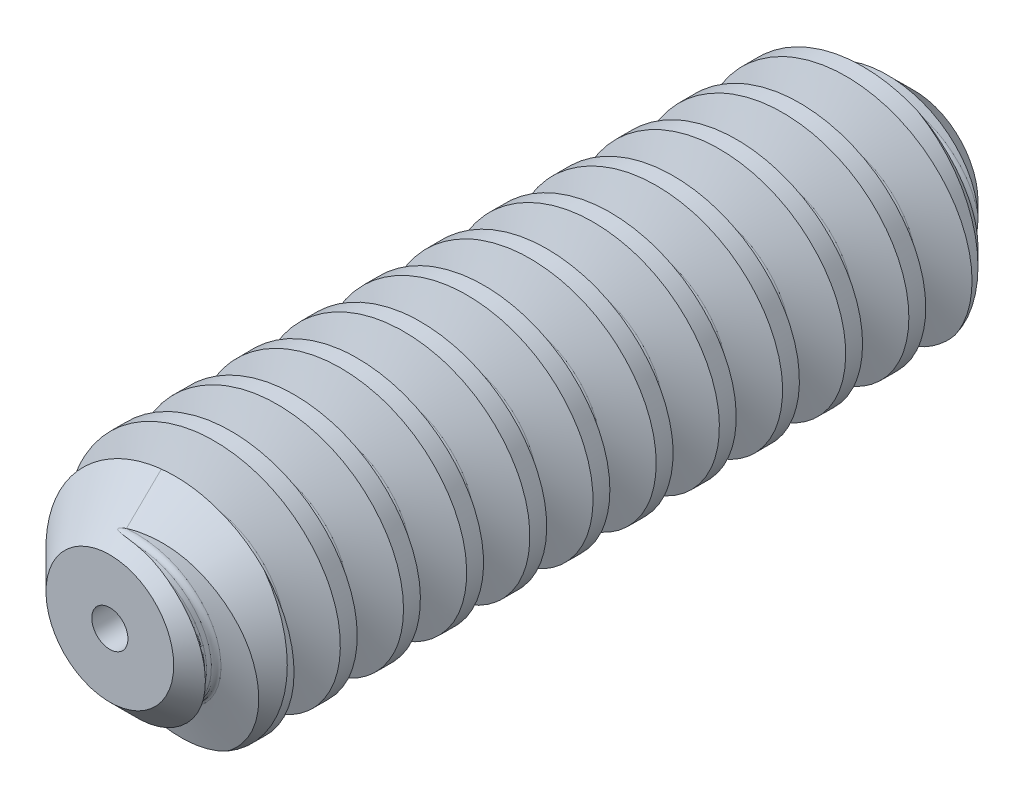
SolidWorks part; units mm, degrees
note: '?' marks a value the reader was unsure of.
ref_plane "Front Plane" through (0, 0, 0) normal (0, 0, 1) x (1, 0, 0)
ref_plane "Top Plane" through (0, 0, 0) normal (0, 1, 0) x (1, 0, 0)
ref_plane "Right Plane" through (0, 0, 0) normal (1, 0, 0) x (0, 0, -1)
ref_axis "Axis1" through (0, 0, 31.1561) along (0, 0, -1)?
sketch "SketchRevolveWorm01" plane through (0, 0, 0) normal (1, 0, 0) x (0, 0, -1)
  line L0 (0, 0) -> (1, 0) construction
  line L1 (10, 0) -> (10, 1.5878)
  line L2 (10, 1.5878) -> (8.5878, 3)
  line L3 (8.5878, 3) -> (-8.5878, 3)
  line L4 (-8.5878, 3) -> (-10, 1.5878)
  line L5 (-10, 1.5878) -> (-10, 0)
  line L6 (-10, 0) -> (10, 0)
  dimension "Side1" = 10
  dimension "ChamferX" = 1.4122
  dimension "ChamferY" = 1.4122
  dimension "OutsideDiameter" = 3
  dimension "WormLength" = 20
revolve "Worm01" add sketch "SketchRevolveWorm01" angle 360 about L0
ref_plane "HelixPlaneWorm01" through (0, 0, 10.9956) normal (0, 0, 1) x (1, 0, 0)
sketch "SketchHelixWorm01" plane through (0, 0, 10.9956) normal (0, 0, 1) x (1, 0, 0)
  circle A0 centre (0, 0) radius 2.5
  dimension "PitchDiameter" = 5
curve "GearHelixWorm01" pitch 1.5708 height 21.9911 turns 14
sketch "SketchToothWorm01" plane through (0, 0, 0) normal (0, 1, 0) x (1, 0, 0)
  line L0 (3.125, -10.3742) -> (1.9735, -10.7956)
  line L1 (1.875, -10.9364) -> (1.875, -11.0547)
  line L2 (1.9735, -11.1956) -> (3.125, -11.617)
  line L3 (3.125, -11.617) -> (3.125, -10.3742)
  arc A0 (1.9735, -10.7956) -> (1.875, -10.9364) centre (2.025, -10.9364) ccw
  arc A1 (1.875, -11.0547) -> (1.9735, -11.1956) centre (2.025, -11.0547) ccw
sweep "ToothCutWorm01" cut profiles "SketchToothWorm01" path "GearHelixWorm01"
sketch "BoreRevolveSketch" plane through (0, 0, 0) normal (1, 0, 0) x (0, 0, -1)
  line L0 (-10, 0) -> (10, 0)
  line L1 (10, 0) -> (10, 0.45)
  line L2 (10, 0.45) -> (-10, 0.45)
  line L3 (-10, 0.45) -> (-10, 0)
  dimension "BoreSide1" = 10
  dimension "TaperSide1" = 0.45
  dimension "BoreSide2" = 10
  dimension "TaperSide2" = 0.45
sketch "KeywaySketch" plane through (0, 0, 0) normal (0, 0, 1) x (1, 0, 0)
  line L0 (0, 0) -> (0.8988, 0) construction
sketch "AuxiliarySketchWorm01" plane through (0, 0, 0) normal (0, 0, 1) x (1, 0, 0)
  circle A0 centre (0, 0) radius 2.5 construction
  dimension "PitchDiameter" = 5
sketch "Sketch7" plane through (0, 0, 10) normal (0, 0, 1) x (1, 0, 0)
  circle A0 centre (0, 0) radius 0.45
extrude "Cut-Extrude2" cut sketch "Sketch7" against normal blind 20
